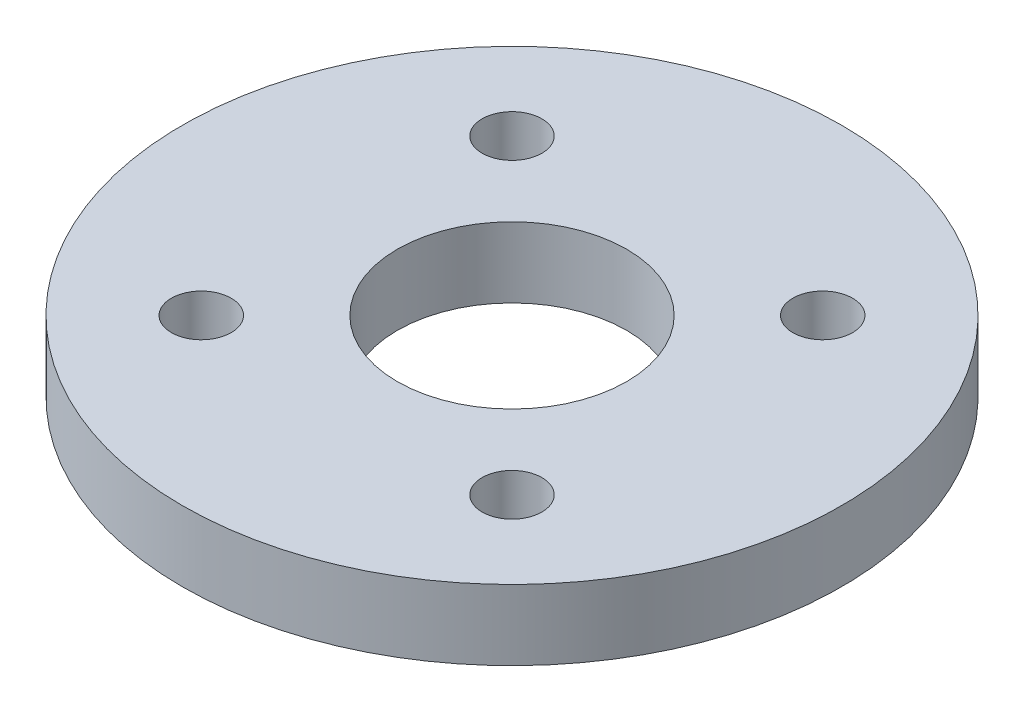
SolidWorks part; units mm, degrees
ref_plane "Front Plane" through (0, 0, 0) normal (0, 0, 1) x (1, 0, 0)
ref_plane "Top Plane" through (0, 0, 0) normal (0, 1, 0) x (1, 0, 0)
ref_plane "Right Plane" through (0, 0, 0) normal (1, 0, 0) x (0, 0, -1)
sketch "Sketch1" plane through (0, 0, 0) normal (0, 1, 0) x (1, 0, 0)
  line L1 (8.8388, 8.8388) -> (-8.8388, 8.8388) construction
  line L2 (-8.8388, 8.8388) -> (-8.8388, -8.8388) construction
  line L3 (-8.8388, -8.8388) -> (8.8388, -8.8388) construction
  line L4 (8.8388, -8.8388) -> (8.8388, 8.8388) construction
  circle A0 centre (0, 0) radius 18.75
  circle A1 centre (0, 0) radius 12.5 construction
  circle A2 centre (-8.8388, 8.8388) radius 1.7
  circle A3 centre (-8.8388, -8.8388) radius 1.7
  circle A4 centre (8.8388, -8.8388) radius 1.7
  circle A5 centre (8.8388, 8.8388) radius 1.7
  circle A6 centre (0, 0) radius 6.525
  dimension "D1" = 25
  dimension "D2" = 3.4
  dimension "D3" = 37.5
  dimension "D4" = 13.05
extrude "Boss-Extrude1" add sketch "Sketch1" along normal blind 4 contours A0 A5 L4 A4 L3 A3 L2 A2 L1 | A5 L1 A2 L2 A3 L3 A4 L4 region at (-18.2197, 0, 0)
